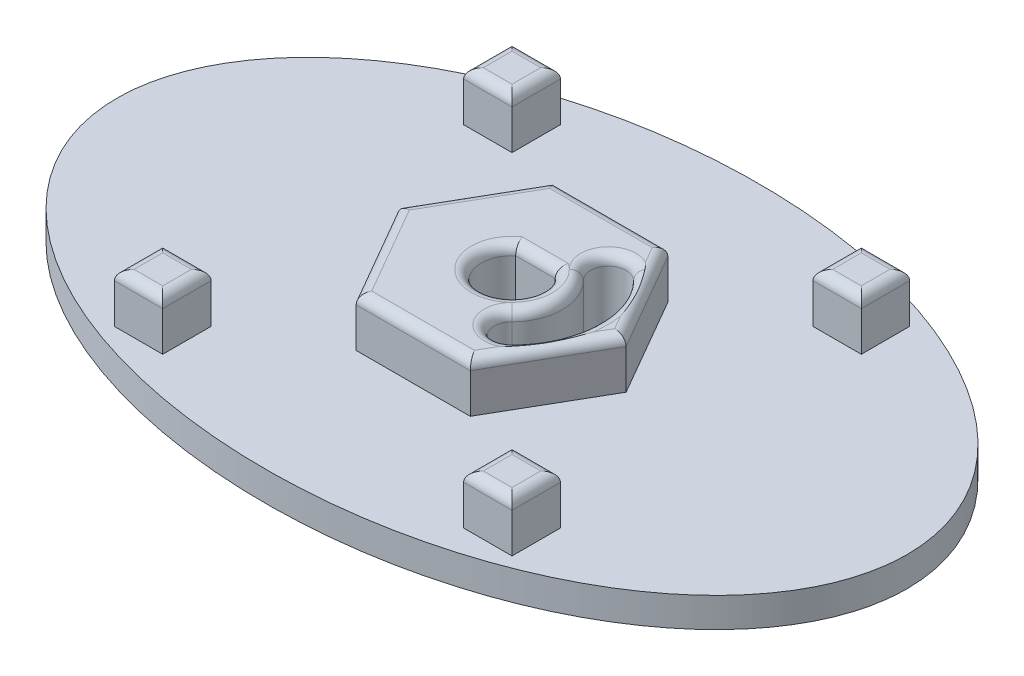
SolidWorks part; units mm, degrees
ref_plane "Front Plane" through (0, 0, 0) normal (0, 0, 1) x (1, 0, 0)
ref_plane "Top Plane" through (0, 0, 0) normal (0, 1, 0) x (1, 0, 0)
ref_plane "Right Plane" through (0, 0, 0) normal (1, 0, 0) x (0, 0, -1)
sketch "Sketch1" plane through (0, 0, 0) normal (0, 1, 0) x (-1, 0, 0)
  line L0 (-1000, 0) -> (49000, 0) construction
  line L1 (11.547, 0) -> (5.7735, 10)
  line L2 (5.7735, 10) -> (-5.7735, 10)
  line L3 (-5.7735, 10) -> (-11.547, 0)
  line L4 (-11.547, 0) -> (-5.7735, -10)
  line L5 (-5.7735, -10) -> (5.7735, -10)
  line L6 (5.7735, -10) -> (11.547, 0)
  line L7 (-20.1277, 15.2277) -> (-15.2277, 15.2277)
  line L8 (-20.1277, 15.2277) -> (-20.1277, 20.1277)
  line L9 (-20.1277, 20.1277) -> (-15.2277, 20.1277)
  line L10 (-15.2277, 15.2277) -> (-15.2277, 20.1277)
  line L11 (-20.1277, 15.2277) -> (-15.2277, 20.1277) construction
  line L12 (-20.1277, 20.1277) -> (-15.2277, 15.2277) construction
  line L13 (0, 0) -> (-17.6777, 17.6777) construction
  line L14 (15.2277, 20.1277) -> (20.1277, 20.1277)
  line L15 (15.2277, 20.1277) -> (15.2277, 15.2277)
  line L16 (15.2277, 15.2277) -> (20.1277, 15.2277)
  line L17 (20.1277, 20.1277) -> (20.1277, 15.2277)
  line L18 (20.1277, -15.2277) -> (20.1277, -20.1277)
  line L19 (20.1277, -15.2277) -> (15.2277, -15.2277)
  line L20 (15.2277, -15.2277) -> (15.2277, -20.1277)
  line L21 (20.1277, -20.1277) -> (15.2277, -20.1277)
  line L22 (-15.2277, -20.1277) -> (-20.1277, -20.1277)
  line L23 (-15.2277, -20.1277) -> (-15.2277, -15.2277)
  line L24 (-15.2277, -15.2277) -> (-20.1277, -15.2277)
  line L25 (-20.1277, -20.1277) -> (-20.1277, -15.2277)
  line L26 (0, 0) -> (-15.2277, 15.2277) construction
  line L27 (0, 0) -> (15.2277, 15.2277) construction
  line L28 (-2, -2.3685) -> (2, -2.3685)
  line L29 (-2.6317, -4.3685) -> (2.6317, -4.3685)
  circle A1 centre (0, 0) radius 10 construction
  circle A2 centre (0, 0) radius 25 construction
  arc A3 (2, -2.3685) -> (-2, -2.3685) centre (0, 0) ccw
  circle A4 centre (0, 0) radius 6.9 construction
  arc A5 (2.6317, -4.3685) -> (-2.6317, -4.3685) centre (0, 0) ccw
  arc A6 (-4.879, -4.879) -> (-4.879, 4.879) centre (0, 0) cw construction
  arc A7 (-6.1518, 6.1518) -> (-6.1518, -6.1518) centre (0, 0) ccw
  arc A8 (-3.6062, 3.6062) -> (-3.6062, -3.6062) centre (0, 0) ccw
  arc A9 (-3.6062, 3.6062) -> (-6.1518, 6.1518) centre (-4.879, 4.879) ccw
  arc A10 (-6.1518, -6.1518) -> (-3.6062, -3.6062) centre (-4.879, -4.879) ccw
  circle A11 centre (0, 0) radius 15
  circle A12 centre (0, 0) radius 13
  ellipse E0 centre (0, 0) end of major axis (-40, 0) minor radius 25
  point P3 (-17.6777, 17.6777)
  point P40 (-6.9, 0)
  dimension "D1" = 50
  dimension "D2" = 20
  dimension "D7" = 6.2
  dimension "D9" = 13.8
  dimension "D12" = 30
  dimension "D3" = 4.9
  dimension "D4" = 45
  dimension "D6" = 90
  dimension "D8" = 4
  dimension "D11" = 40
  dimension "D10" = 2
  dimension "D13" = 2
  dimension "D5" = 4
extrude "Boss-Extrude1" add sketch "Sketch1" along normal blind 5 contours L5 L6 L1 L2 L3 L4 A10 A7 A9 A5 L29 | L29 A5 A3 L28 | L8 L7 L10 L9 | L14 L17 L16 L15 | L18 L21 L20 L19 | L22 L25 L24 L23 region at (-8.3957, 0, -4.8472) region at (3.0564, 0, -3.9074)
extrude "Boss-Extrude2" add sketch "Sketch1<3>" against normal blind 3 contours E0 L22 L25 L24 L23 L18 L21 L20 L19 L14 L17 L16 L15 L10 L7 L8 L9 A11 | L5 L6 L1 L2 L3 L4 A10 A7 A9 A5 L29 | A11 L6 L5 L4 L3 L2 L1 | L29 A5 A3 L28 | A11 A12 | L25 L22 L23 L24 | L21 L18 L19 L20 | L17 L14 L15 L16 | L7 L10 L9 L8 region at (-8.3957, 0, -4.8472) region at (17.6777, 0, 17.6777) region at (-17.6777, 0, 17.6777) region at (-17.6777, 0, -17.6777) region at (17.6777, 0, -17.6777) region at (3.0564, 0, -3.9074) region at (14.5757, 0, 0) region at (12.6323, 0, 0) region at (-39.0565, 0, 0.0407)
sketch "Sketch1<3>" plane through (0, 0, 0) normal (0, 1, 0) x (-1, 0, 0) same geometry as "Sketch1"
extrude "Boss-Extrude3" add sketch "Sketch1<5>" against normal blind 5 from offset 3 contours L29 A5 A3 L28 | A11 A12 region at (3.0564, 0, -3.9074) region at (14.5757, 0, 0) offset against normal yes
sketch "Sketch1<5>" plane through (0, 0, 0) normal (0, 1, 0) x (-1, 0, 0) same geometry as "Sketch1"
fillet "Fillet1" radius 1 34 edges at (0, -8, 5.1) (0, -8, -4.3685) (0, -8, -2.3685) (0, -8, 3.1) (0, 5, -2.3685) (0, 5, 3.1) (8.6603, 5, -5) (8.6603, 5, 5) (0, 5, 10) (-8.6603, 5, 5) (-8.6603, 5, -5) (0, 5, -10) (8.7, 5, 0) (3.6062, 5, -6.1518) (5.1, 5, 0) (3.6062, 5, 6.1518) (-17.6777, 5, 20.1277) (-20.1277, 5, 17.6777) (-17.6777, 5, 15.2277) (-15.2277, 5, 17.6777) (15.2277, 5, 17.6777) (17.6777, 5, 15.2277) (20.1277, 5, 17.6777) (17.6777, 5, 20.1277) (17.6777, 5, -20.1277) (20.1277, 5, -17.6777) (17.6777, 5, -15.2277) (15.2277, 5, -17.6777) (-20.1277, 5, -17.6777) (-17.6777, 5, -20.1277) (-15.2277, 5, -17.6777) (-17.6777, 5, -15.2277) (0, -3, 13) (0, -3, 15)
ref_axis "Axis1" through (0, 4, 0) along (0, -1, 0)
